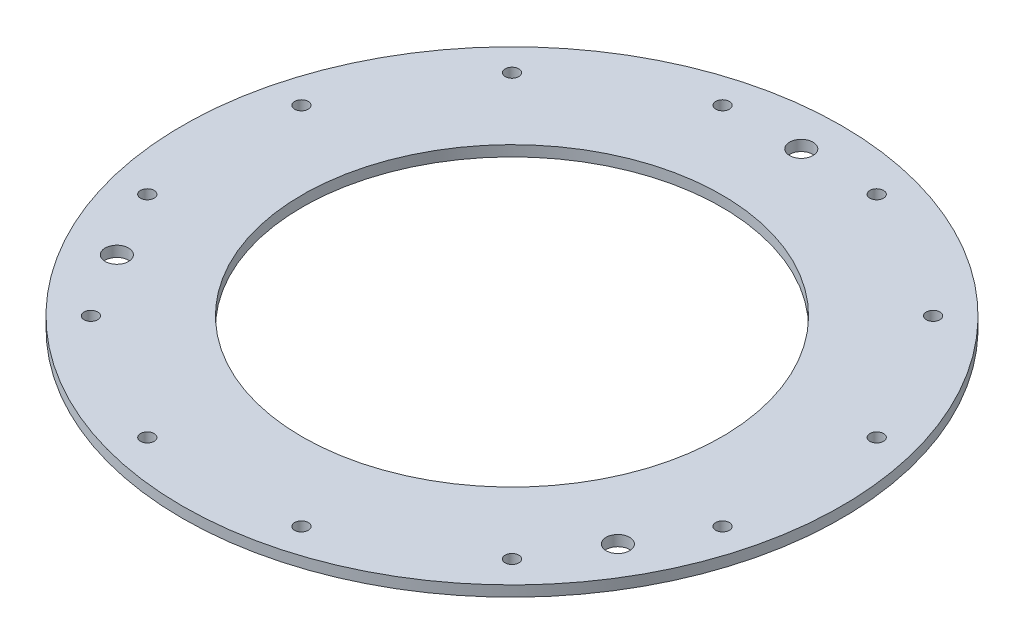
SolidWorks part; units mm, degrees
material "1060 Alloy"
ref_plane "Ebene vorne" through (0, 0, 0) normal (0, 0, 1) x (1, 0, 0)
ref_plane "Ebene oben" through (0, 0, 0) normal (0, 1, 0) x (1, 0, 0)
ref_plane "Ebene rechts" through (0, 0, 0) normal (1, 0, 0) x (0, 0, -1)
sketch "Sketch1" plane through (0, 0, 0) normal (0, 1, 0) x (1, 0, 0)
  circle A0 centre (0, 0) radius 49.3
  circle A1 centre (0, 0) radius 77.47
  dimension "D1" = 154.94
  dimension "D2" = 98.6
extrude "Boss-Extrude1" add sketch "Sketch1" along normal blind 2.5
sketch "Sketch2" plane through (0, 2.5, 0) normal (0, 1, 0) x (1, 0, 0)
  line L0 (18.1173, 67.6148) -> (0, 0) construction
  line L1 (0, 0) -> (-18.1173, 67.6148) construction
  line L2 (-18.1173, 67.6148) -> (18.1173, 67.6148) construction
  circle A0 centre (-18.1173, 67.6148) radius 1.6
  circle A1 centre (18.1173, 67.6148) radius 1.6
  circle A2 centre (49.4975, 49.4975) radius 1.6
  circle A3 centre (67.6148, 18.1173) radius 1.6
  circle A4 centre (67.6148, -18.1173) radius 1.6
  circle A5 centre (49.4975, -49.4975) radius 1.6
  circle A6 centre (18.1173, -67.6148) radius 1.6
  circle A7 centre (-18.1173, -67.6148) radius 1.6
  circle A8 centre (-49.4975, -49.4975) radius 1.6
  circle A9 centre (-67.6148, -18.1173) radius 1.6
  circle A10 centre (-67.6148, 18.1173) radius 1.6
  circle A11 centre (-49.4975, 49.4975) radius 1.6
  point P28 (0, 0)
  dimension "D1" = 3.2
  dimension "D2" = 70
  dimension "D3" = 12
extrude "Cut-Extrude1" cut sketch "Sketch2" against normal through all
hole_wizard "Dégagement M52" positions "Esquisse3" profile "Esquisse4" hole size "M5" standard "DIN" end condition through all
sketch "Esquisse3" plane through (0, 2.5, 0) normal (0, 1, 0) x (1, 0, 0)
  line L0 (0, 68) -> (-58.8897, -34) construction
  line L1 (-58.8897, -34) -> (58.8897, -34) construction
  line L2 (58.8897, -34) -> (0, 68) construction
  line L4 (0, 0) -> (0, 68) construction
  circle A0 centre (0, 0) radius 68 construction
  point P0 (0, 68)
  point P2 (-58.8897, -34)
  point P4 (58.8897, -34)
  point P23 (62.1909, -27.5008)
  point P24 (0, 0)
  point P25 (0, 54.5405)
  point P26 (0, 0)
  point P27 (0, 56.3435)
  dimension "D1" = 136
  dimension "D2" = 60
  dimension "D3" = 60
sketch "Esquisse4" plane through (0, 2.5, -68) normal (1, 0, 0) x (0, 0, 1)
  line L0 (0, 0) -> (0, 2.5)
  line L1 (0, 2.5) -> (2.75, 2.5)
  line L2 (2.75, 2.5) -> (2.75, 0)
  line L5 (2.75, 0) -> (0, 0)
  line L11 (0, -6.35) -> (0, 107.95) construction
  dimension "Diamètre du perçage jusqu'au prochain" = 5.5
  dimension "Profondeur du perçage jusqu'au prochain" = 2.5
